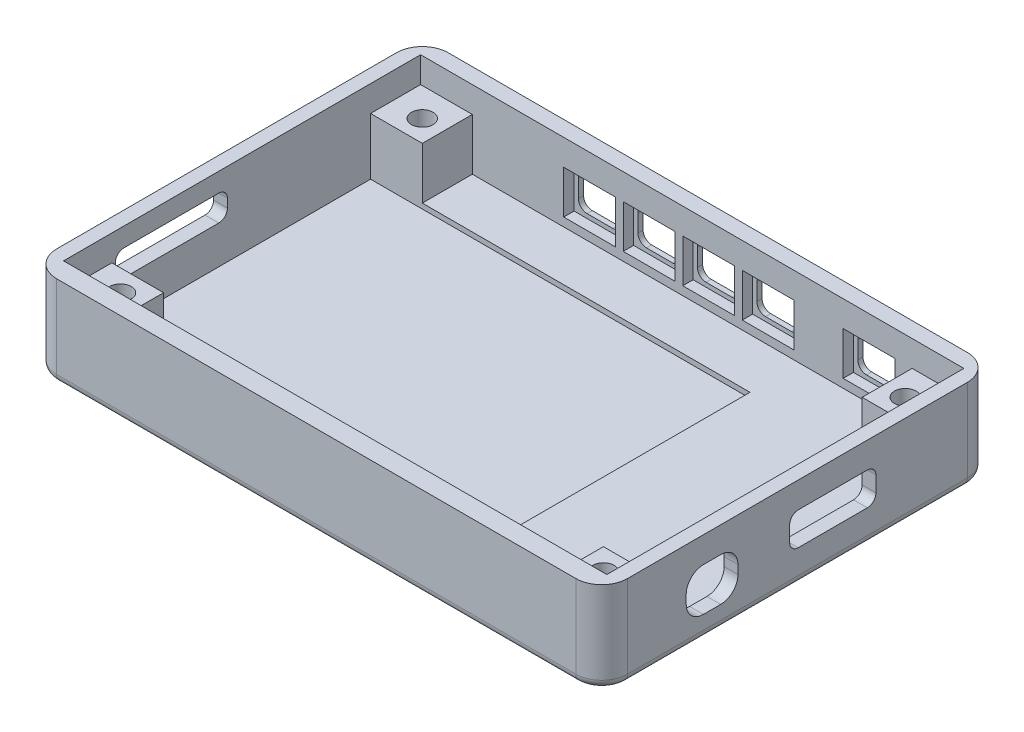
SolidWorks part; units mm, degrees
ref_plane "前视基准面" through (0, 0, 0) normal (0, 0, 1) x (1, 0, 0)
ref_plane "上视基准面" through (0, 0, 0) normal (0, 1, 0) x (1, 0, 0)
ref_plane "右视基准面" through (0, 0, 0) normal (1, 0, 0) x (0, 0, -1)
sketch "草图1" plane through (0, 0, 0) normal (0, 1, 0) x (1, 0, 0)
  line L1 (-31.5, -21) -> (31.5, -21)
  line L2 (-31.5, -21) -> (-31.5, 21)
  line L3 (-31.5, 21) -> (31.5, 21)
  line L4 (31.5, -21) -> (31.5, 21)
  line L5 (-31.5, -21) -> (31.5, 21) construction
  line L6 (-31.5, 21) -> (31.5, -21) construction
  point P0 (0, 0)
  dimension "D1" = 63
  dimension "D2" = 42
extrude "底" add sketch "草图1" against normal blind 1.6
sketch "草图2" plane through (0, 0, 0) normal (0, 1, 0) x (1, 0, 0)
  line L0 (-31.5, 21) -> (-31.5, -21) construction
  line L1 (-31.5, -15) -> (12.5, -15)
  line L2 (-31.5, -15) -> (-31.5, 15)
  line L3 (-31.5, 15) -> (12.5, 15)
  line L4 (12.5, -15) -> (12.5, 15)
  line L5 (-31.5, -15) -> (12.5, 15) construction
  line L6 (-31.5, 15) -> (12.5, -15) construction
  line L7 (31.5, 21) -> (-31.5, 21) construction
  line L8 (-31.5, -21) -> (31.5, -21) construction
  point P0 (-19.9597, 0.5003)
  dimension "D1" = 44
  dimension "D2" = 6
  dimension "D3" = 0
  dimension "D4" = 6
extrude "电池槽" cut sketch "草图2" against normal blind 0.6
sketch "草图4" plane through (0, -1.6, 0) normal (0, -1, 0) x (-1, 0, 0)
  line L0 (-31.5, 21) -> (-31.5, -21)
  line L1 (-31.5, 21) -> (-33.1, 21)
  line L2 (-31.5, -21) -> (-33.1, -21)
  line L3 (-33.1, 21) -> (-33.1, -21)
  line L4 (31.5, 21) -> (31.5, -21)
  line L5 (31.5, 21) -> (33.1, 21)
  line L6 (31.5, -21) -> (33.1, -21)
  line L7 (33.1, 21) -> (33.1, -21)
  dimension "D1" = 1.6
  dimension "D2" = 1.6
extrude "侧边" add sketch "草图4" against normal blind 10.6
sketch "草图5" plane through (0, 0, 0) normal (0, 1, 0) x (1, 0, 0)
  line L0 (-31.5, 21) -> (-31.5, 15)
  line L1 (-31.5, 21) -> (-25.5, 21)
  line L2 (-31.5, 15) -> (-25.5, 15)
  line L3 (-25.5, 21) -> (-25.5, 15)
  line L4 (-31.5, 21) -> (-31.5, 15) construction
  line L5 (25.5, 21) -> (25.5, 15)
  line L6 (25.5, 21) -> (31.5, 21)
  line L7 (25.5, 15) -> (31.5, 15)
  line L8 (31.5, 21) -> (31.5, 15)
  line L9 (-31.5, -15) -> (-31.5, -21)
  line L10 (-31.5, -15) -> (-25.5, -15)
  line L11 (-31.5, -21) -> (-25.5, -21)
  line L12 (-25.5, -15) -> (-25.5, -21)
  line L13 (25.5, -15) -> (25.5, -21)
  line L14 (25.5, -15) -> (31.5, -15)
  line L15 (25.5, -21) -> (31.5, -21)
  line L16 (31.5, -15) -> (31.5, -21)
  dimension "D1" = 6
  dimension "D2" = 6
  dimension "D3" = 6
  dimension "D4" = 6
extrude "螺丝固定" add sketch "草图5" along normal offset from surface (6 mm away) 3 up to face at (-32.3, 9, 0)
sketch "草图6" plane through (0, 9, 0) normal (0, 1, 0) x (1, 0, 0)
  line L0 (-25.5, 15) -> (-25.5, 21) construction
  line L1 (-31.5, 15) -> (-25.5, 15) construction
  circle A0 centre (-28, 17.5) radius 1.25
  circle A1 centre (28, 17.5) radius 1.25
  circle A2 centre (28, -17.5) radius 1.25
  circle A3 centre (-28, -17.5) radius 1.25
  dimension "D1" = 2.5
  dimension "D2" = 2.5
  dimension "D3" = 2.5
  dimension "D4" = 2
  dimension "D5" = 2
extrude "螺丝孔" cut sketch "草图6" against normal up to surface (9 mm away) up to face at (7.3333, 0, 0)
sketch "草图8" plane through (0, 0, 0) normal (0, 1, 0) x (1, 0, 0)
  line L0 (25.5, 21) -> (25.5, 15) construction
  line L1 (-30.5, 20) -> (-25.5, 20)
  line L2 (-30.5, 20) -> (-30.5, 15)
  line L3 (-30.5, 15) -> (-25.5, 15)
  line L4 (-25.5, 20) -> (-25.5, 15)
  line L5 (-30.5, 20) -> (-25.5, 15) construction
  line L6 (-30.5, 15) -> (-25.5, 20) construction
  line L7 (30.5, 20) -> (25.5, 20)
  line L8 (30.5, 20) -> (30.5, 15)
  line L9 (30.5, 15) -> (25.5, 15)
  line L10 (25.5, 20) -> (25.5, 15)
  line L11 (30.5, 20) -> (25.5, 15) construction
  line L12 (30.5, 15) -> (25.5, 20) construction
  line L14 (-30.5, -20) -> (-25.5, -20)
  line L15 (-30.5, -20) -> (-30.5, -15)
  line L16 (-30.5, -15) -> (-25.5, -15)
  line L17 (-25.5, -20) -> (-25.5, -15)
  line L18 (-30.5, -20) -> (-25.5, -15) construction
  line L19 (-30.5, -15) -> (-25.5, -20) construction
  line L20 (30.5, -20) -> (25.5, -20)
  line L21 (30.5, -20) -> (30.5, -15)
  line L22 (30.5, -15) -> (25.5, -15)
  line L23 (25.5, -20) -> (25.5, -15)
  line L24 (30.5, -20) -> (25.5, -15) construction
  line L25 (30.5, -15) -> (25.5, -20) construction
  circle A0 centre (28, 17.5) radius 1.25 construction
  circle A1 centre (28, -17.5) radius 1.25 construction
  circle A2 centre (-28, -17.5) radius 1.25 construction
  circle A3 centre (-28, 17.5) radius 1.25 construction
  circle A4 centre (28, 17.5) radius 1.25 construction
  circle A5 centre (28, -17.5) radius 1.25 construction
  circle A6 centre (-28, -17.5) radius 1.25 construction
  circle A7 centre (-28, 17.5) radius 1.25 construction
sketch "草图9" plane through (0, 0, -21) normal (0, 0, -1) x (-1, 0, 0)
  line L0 (-33.1, 9) -> (-33.1, -1.6)
  line L1 (-33.1, 9) -> (33.1, 9)
  line L2 (-33.1, -1.6) -> (33.1, -1.6)
  line L3 (33.1, 9) -> (33.1, -1.6)
extrude "凸台-拉伸4" add sketch "草图9" along normal blind 1.6
sketch "草图10" plane through (0, 0, -21) normal (0, 0, 1) x (1, 0, 0)
  line L1 (17.5, 1) -> (23.5, 1)
  line L2 (17.5, 1) -> (17.5, 6)
  line L3 (17.5, 6) -> (23.5, 6)
  line L4 (23.5, 1) -> (23.5, 6)
  line L5 (17.5, 1) -> (23.5, 6) construction
  line L6 (17.5, 6) -> (23.5, 1) construction
  line L7 (25.5, 0) -> (-25.5, 0) construction
  line L8 (25.5, 6) -> (25.5, 0) construction
  line L9 (5.8, 1) -> (11.8, 1)
  line L10 (5.8, 1) -> (5.8, 6)
  line L11 (5.8, 6) -> (11.8, 6)
  line L12 (11.8, 1) -> (11.8, 6)
  line L13 (5.8, 1) -> (11.8, 6) construction
  line L14 (5.8, 6) -> (11.8, 1) construction
  line L15 (-1.1, 1) -> (4.9, 1)
  line L16 (-1.1, 1) -> (-1.1, 6)
  line L17 (-1.1, 6) -> (4.9, 6)
  line L18 (4.9, 1) -> (4.9, 6)
  line L19 (-1.1, 1) -> (4.9, 6) construction
  line L20 (-1.1, 6) -> (4.9, 1) construction
  line L21 (-8, 1) -> (-2, 1)
  line L22 (-8, 1) -> (-8, 6)
  line L23 (-8, 6) -> (-2, 6)
  line L24 (-2, 1) -> (-2, 6)
  line L25 (-8, 1) -> (-2, 6) construction
  line L26 (-8, 6) -> (-2, 1) construction
  line L27 (-14.9, 1) -> (-8.9, 1)
  line L28 (-14.9, 1) -> (-14.9, 6)
  line L29 (-14.9, 6) -> (-8.9, 6)
  line L30 (-8.9, 1) -> (-8.9, 6)
  line L31 (-14.9, 1) -> (-8.9, 6) construction
  line L32 (-14.9, 6) -> (-8.9, 1) construction
  point P0 (20.5, 3.5)
  point P11 (8.8, 3.5)
  point P16 (1.9, 3.5)
  point P21 (-5, 3.5)
  point P26 (-11.9, 3.5)
  dimension "D1" = 6
  dimension "D2" = 5
  dimension "D3" = 5
  dimension "D4" = 3.5
  dimension "D5" = 2
  dimension "D6" = 4
extrude "按键底" cut sketch "草图10" against normal blind 1
sketch "草图12" plane through (0, 0, -22) normal (0, 0, 1) x (1, 0, 0)
  line L0 (17.5, 6) -> (23.5, 1) construction
  line L1 (6.3, 2.5) -> (6.3, 4.5)
  line L2 (19, 1.5) -> (22, 1.5)
  line L3 (18, 2.5) -> (18, 4.5)
  line L4 (23.5, 1) -> (23.5, 6)
  line L5 (23.5, 6) -> (17.5, 6)
  line L6 (17.5, 6) -> (17.5, 1)
  line L7 (17.5, 1) -> (23.5, 1)
  line L8 (23.5, 1) -> (23.5, 6) construction
  line L9 (23.5, 6) -> (17.5, 6) construction
  line L10 (17.5, 6) -> (17.5, 1) construction
  line L11 (17.5, 1) -> (23.5, 1) construction
  line L12 (19, 5.5) -> (22, 5.5)
  line L13 (23, 2.5) -> (23, 4.5)
  line L14 (18, 1.5) -> (23, 5.5) construction
  line L15 (18, 5.5) -> (23, 1.5) construction
  line L16 (7.3, 1.5) -> (10.3, 1.5)
  line L17 (7.3, 5.5) -> (10.3, 5.5)
  line L18 (11.3, 2.5) -> (11.3, 4.5)
  line L19 (-0.6, 2.5) -> (-0.6, 4.5)
  line L20 (0.4, 1.5) -> (3.4, 1.5)
  line L21 (0.4, 5.5) -> (3.4, 5.5)
  line L22 (4.4, 2.5) -> (4.4, 4.5)
  line L23 (-7.5, 2.5) -> (-7.5, 4.5)
  line L24 (-6.5, 1.5) -> (-3.5, 1.5)
  line L25 (-6.5, 5.5) -> (-3.5, 5.5)
  line L26 (-2.5, 2.5) -> (-2.5, 4.5)
  line L27 (-14.4, 2.5) -> (-14.4, 4.5)
  line L28 (-13.4, 1.5) -> (-10.4, 1.5)
  line L29 (-13.4, 5.5) -> (-10.4, 5.5)
  line L30 (-9.4, 2.5) -> (-9.4, 4.5)
  arc A0 (22, 5.5) -> (23, 4.5) centre (22, 4.5) cw
  arc A1 (22, 1.5) -> (23, 2.5) centre (22, 2.5) ccw
  arc A2 (19, 1.5) -> (18, 2.5) centre (19, 2.5) cw
  arc A3 (18, 4.5) -> (19, 5.5) centre (19, 4.5) cw
  arc A4 (6.3, 4.5) -> (7.3, 5.5) centre (7.3, 4.5) cw
  arc A5 (7.3, 1.5) -> (6.3, 2.5) centre (7.3, 2.5) cw
  arc A6 (10.3, 5.5) -> (11.3, 4.5) centre (10.3, 4.5) cw
  arc A7 (10.3, 1.5) -> (11.3, 2.5) centre (10.3, 2.5) ccw
  arc A8 (-0.6, 4.5) -> (0.4, 5.5) centre (0.4, 4.5) cw
  arc A9 (0.4, 1.5) -> (-0.6, 2.5) centre (0.4, 2.5) cw
  arc A10 (3.4, 5.5) -> (4.4, 4.5) centre (3.4, 4.5) cw
  arc A11 (3.4, 1.5) -> (4.4, 2.5) centre (3.4, 2.5) ccw
  arc A12 (-7.5, 4.5) -> (-6.5, 5.5) centre (-6.5, 4.5) cw
  arc A13 (-6.5, 1.5) -> (-7.5, 2.5) centre (-6.5, 2.5) cw
  arc A14 (-3.5, 5.5) -> (-2.5, 4.5) centre (-3.5, 4.5) cw
  arc A15 (-3.5, 1.5) -> (-2.5, 2.5) centre (-3.5, 2.5) ccw
  arc A16 (-14.4, 4.5) -> (-13.4, 5.5) centre (-13.4, 4.5) cw
  arc A17 (-13.4, 1.5) -> (-14.4, 2.5) centre (-13.4, 2.5) cw
  arc A18 (-10.4, 5.5) -> (-9.4, 4.5) centre (-10.4, 4.5) cw
  arc A19 (-10.4, 1.5) -> (-9.4, 2.5) centre (-10.4, 2.5) ccw
  point P2 (20.5, 3.5)
  dimension "D4" = 1
  dimension "D2" = 5
  dimension "D3" = 4
  dimension "D1" = 0
  dimension "D5" = 2
  dimension "D6" = 4
extrude "按键头" cut sketch "草图12" against normal up to next
fillet "圆角4" radius 1 3 edges at (-33.1, -1.6, -0.8) (33.1, -1.6, -0.8) (0, -1.6, -22.6)
fillet "圆角5" radius 3 4 edges at (-32.8071, -1.3071, -22.3071) (32.8071, -1.3071, -22.3071) (33.1, 4.2, -22.6) (-33.1, 4.2, -22.6)
sketch "草图15" plane through (0, 9, 0) normal (0, 1, 0) x (1, 0, 0)
  line L8 (-31.5, 21) -> (31.5, 21)
  line L10 (-31.5, 21) -> (31.5, 21)
  line L16 (33.1, -21) -> (33.1, 19.6)
  line L17 (30.1, 22.6) -> (-30.1, 22.6)
  line L18 (-33.1, 19.6) -> (-33.1, -21)
  line L19 (-33.1, -21) -> (-31.5, -21)
  line L22 (-31.5, -21) -> (-31.5, 21)
  line L28 (31.5, 21) -> (31.5, -21)
  line L31 (31.5, -21) -> (33.1, -21)
  line L32 (33.1, -21) -> (33.1, 19.6)
  line L33 (30.1, 22.6) -> (-30.1, 22.6)
  line L34 (-33.1, 19.6) -> (-33.1, -21)
  line L35 (-33.1, -21) -> (-31.5, -21)
  line L38 (-31.5, -21) -> (-31.5, 21)
  line L44 (31.5, 21) -> (31.5, -21)
  line L47 (31.5, -21) -> (33.1, -21)
  arc A2 (33.1, 19.6) -> (30.1, 22.6) centre (30.1, 19.6) ccw
  arc A3 (-30.1, 22.6) -> (-33.1, 19.6) centre (-30.1, 19.6) ccw
  arc A4 (33.1, 19.6) -> (30.1, 22.6) centre (30.1, 19.6) ccw
  arc A5 (-30.1, 22.6) -> (-33.1, 19.6) centre (-30.1, 19.6) ccw
  dimension "D1" = 0
sketch "草图16" plane through (-31.5, 0, 0) normal (1, 0, 0) x (0, 0, -1)
  line L1 (-14.6, 5.8) -> (-14.6, 4.8)
  line L2 (-1.6, 5.8) -> (-1.6, 4.8)
  line L3 (-13.6, 3.8) -> (-2.6, 3.8)
  line L4 (-21, 9) -> (21, 9) construction
  line L5 (-15, 6) -> (-15, -0.6) construction
  line L6 (-13.6, 6.8) -> (-2.6, 6.8)
  arc A0 (-14.6, 4.8) -> (-13.6, 3.8) centre (-13.6, 4.8) ccw
  arc A1 (-1.6, 4.8) -> (-2.6, 3.8) centre (-2.6, 4.8) cw
  arc A2 (-13.6, 6.8) -> (-14.6, 5.8) centre (-13.6, 5.8) ccw
  arc A3 (-2.6, 6.8) -> (-1.6, 5.8) centre (-2.6, 5.8) cw
  point P10 (-14.6, 3.8)
  point P13 (-1.6, 3.8)
  dimension "D4" = 1
  dimension "D2" = 1
  dimension "D1" = 13
  dimension "D3" = 0.4
  dimension "D5" = 2.2
extrude "tf口" cut sketch "草图16" against normal up to next
sketch "草图17" plane through (31.5, 0, 0) normal (-1, 0, 0) x (0, 0, 1)
  line L1 (7, 4) -> (7, 3)
  line L2 (13, 4) -> (13, 3)
  line L3 (9, 1) -> (11, 1)
  line L4 (-21, 9) -> (21, 9) construction
  line L5 (15, -0.6) -> (15, 6) construction
  line L7 (1, 5) -> (1, 3.2)
  line L8 (-9, 5) -> (-9, 3.2)
  line L9 (0, 2.2) -> (-8, 2.2)
  line L10 (-8, 6) -> (0, 6)
  line L12 (9, 6) -> (11, 6)
  arc A0 (13, 3) -> (11, 1) centre (11, 3) cw
  arc A1 (7, 3) -> (9, 1) centre (9, 3) ccw
  arc A2 (1, 3.2) -> (0, 2.2) centre (0, 3.2) cw
  arc A3 (-9, 3.2) -> (-8, 2.2) centre (-8, 3.2) ccw
  arc A4 (0, 6) -> (1, 5) centre (0, 5) cw
  arc A5 (-8, 6) -> (-9, 5) centre (-8, 5) ccw
  arc A6 (11, 6) -> (13, 4) centre (11, 4) cw
  arc A7 (9, 6) -> (7, 4) centre (9, 4) ccw
  point P10 (13, 1)
  point P13 (7, 1)
  point P14 (1, 6)
  point P22 (1, 2.2)
  point P25 (-9, 2.2)
  dimension "D4" = 2
  dimension "D8" = 1
  dimension "D2" = 1
  dimension "D7" = 2
  dimension "D1" = 6
  dimension "D3" = 2
  dimension "D5" = 10
  dimension "D6" = 14
  dimension "D9" = 3
  dimension "D10" = 1.8
  dimension "D11" = 1
extrude "耳机和usb口" cut sketch "草图17" against normal up to next
sketch "草图18" plane through (0, 0, 21) normal (0, 0, 1) x (1, 0, 0)
  line L0 (33.1, 9) -> (33.1, -0.6) construction
  line L1 (-32.1, -1.6) -> (32.1, -1.6) construction
  line L2 (-33.1, 9) -> (-33.1, -0.6) construction
  line L3 (33.1, 9) -> (33.1, -0.6)
  line L4 (-32.1, -1.6) -> (32.1, -1.6)
  line L5 (-33.1, 9) -> (-33.1, -0.6)
  line L6 (-33.1, 9) -> (33.1, 9)
  arc A0 (32.1, -1.6) -> (33.1, -0.6) centre (32.1, -0.6) ccw construction
  arc A1 (-33.1, -0.6) -> (-32.1, -1.6) centre (-32.1, -0.6) ccw construction
  arc A2 (32.1, -1.6) -> (33.1, -0.6) centre (32.1, -0.6) ccw
  arc A3 (-33.1, -0.6) -> (-32.1, -1.6) centre (-32.1, -0.6) ccw
extrude "封底" add sketch "草图18" along normal blind 1.8
fillet "圆角7" radius 3 2 edges at (33.1, 4.2, 22.8) (-33.1, 4.2, 22.8) tangent propagation no
fillet "圆角8" radius 1 3 edges at (-31.1705, -1.6, 22.6025) (31.1705, -1.6, 22.6025) (0, -1.6, 22.8)
sketch "草图19" plane through (0, 0, 21) normal (0, 0, -1) x (-1, 0, 0)
  line L8 (31.5, 9) -> (-31.5, 9)
  line L9 (-31.5, 9) -> (-31.5, 6)
  line L10 (-31.5, 6) -> (-25.5, 6)
  line L11 (-25.5, 6) -> (-25.5, 0)
  line L12 (-25.5, 0) -> (25.5, 0)
  line L13 (25.5, 0) -> (25.5, 6)
  line L14 (25.5, 6) -> (31.5, 6)
  line L15 (31.5, 6) -> (31.5, 9)
  line L16 (31.5, 9) -> (-31.5, 9)
  line L17 (-31.5, 9) -> (-31.5, 6)
  line L18 (-31.5, 6) -> (-25.5, 6)
  line L19 (-25.5, 6) -> (-25.5, 0)
  line L20 (-25.5, 0) -> (25.5, 0)
  line L21 (25.5, 0) -> (25.5, 6)
  line L22 (25.5, 6) -> (31.5, 6)
  line L23 (31.5, 6) -> (31.5, 9)
  dimension "D1" = 0
extrude "凸台-拉伸5" add sketch "草图19" along normal blind 0.4
sketch "草图24" plane through (0, 0, 0) normal (0, 1, 0) x (1, 0, 0)
  line L12 (-25.5, -15) -> (-25.5, -20.6)
  line L13 (-25.5, -20.6) -> (25.5, -20.6)
  line L14 (25.5, -20.6) -> (25.5, -15)
  line L15 (25.5, -15) -> (31.5, -15)
  line L16 (31.5, -15) -> (31.5, 15)
  line L17 (31.5, 15) -> (25.5, 15)
  line L18 (25.5, 15) -> (25.5, 21)
  line L19 (25.5, 21) -> (-25.5, 21)
  line L20 (-25.5, 21) -> (-25.5, 15)
  line L21 (-25.5, 15) -> (12.5, 15)
  line L22 (12.5, 15) -> (12.5, -15)
  line L23 (12.5, -15) -> (-25.5, -15)
  line L24 (-25.5, -15) -> (-25.5, -20.6)
  line L25 (-25.5, -20.6) -> (25.5, -20.6)
  line L26 (25.5, -20.6) -> (25.5, -15)
  line L27 (25.5, -15) -> (31.5, -15)
  line L28 (31.5, -15) -> (31.5, 15)
  line L29 (31.5, 15) -> (25.5, 15)
  line L30 (25.5, 15) -> (25.5, 21)
  line L32 (-25.5, 21) -> (-25.5, 15)
  line L33 (-25.5, 15) -> (12.5, 15)
  line L34 (12.5, 15) -> (12.5, -15)
  line L35 (12.5, -15) -> (-25.5, -15)
  line L37 (25.5, 21) -> (-25.5, 21)
  dimension "D1" = 0
sketch "草图25" plane through (0, 0, 0) normal (0, 1, 0) x (1, 0, 0)
  circle A0 centre (25.5, 12) radius 1
  point P0 (28, 17.5)
  dimension "D1" = 2
  dimension "D2" = 2.5
  dimension "D3" = 5.5
extrude "BOOT孔" cut sketch "草图25" against normal up to next
sketch "草图27" plane through (0, 0, -21) normal (0, 0, 1) x (1, 0, 0)
  line L4 (5.8, 1) -> (11.8, 1)
  line L5 (11.8, 1) -> (11.8, 6)
  line L6 (11.8, 6) -> (5.8, 6)
  line L7 (5.8, 6) -> (5.8, 1)
  line L8 (31.5, 6) -> (31.5, 9)
  line L9 (31.5, 9) -> (-31.5, 9)
  line L10 (-31.5, 9) -> (-31.5, 6)
  line L11 (-31.5, 6) -> (-25.5, 6)
  line L12 (-25.5, 6) -> (-25.5, 0)
  line L13 (-25.5, 0) -> (25.5, 0)
  line L14 (25.5, 0) -> (25.5, 6)
  line L15 (25.5, 6) -> (31.5, 6)
  line L16 (31.5, 6) -> (31.5, 9)
  line L17 (31.5, 9) -> (-31.5, 9)
  line L18 (-31.5, 9) -> (-31.5, 6)
  line L19 (-31.5, 6) -> (-25.5, 6)
  line L20 (-25.5, 6) -> (-25.5, 0)
  line L21 (-25.5, 0) -> (25.5, 0)
  line L22 (25.5, 0) -> (25.5, 6)
  line L23 (25.5, 6) -> (31.5, 6)
  line L24 (5.8, 1) -> (11.8, 1)
  line L25 (11.8, 1) -> (11.8, 6)
  line L26 (11.8, 6) -> (5.8, 6)
  line L27 (5.8, 6) -> (5.8, 1)
  line L28 (17.5, 1) -> (23.5, 1)
  line L29 (23.5, 1) -> (23.5, 6)
  line L30 (23.5, 6) -> (17.5, 6)
  line L31 (17.5, 6) -> (17.5, 1)
  line L32 (17.5, 1) -> (23.5, 1)
  line L33 (23.5, 1) -> (23.5, 6)
  line L34 (23.5, 6) -> (17.5, 6)
  line L35 (17.5, 6) -> (17.5, 1)
  line L36 (-14.9, 1) -> (-8.9, 1)
  line L37 (-8.9, 1) -> (-8.9, 6)
  line L38 (-8.9, 6) -> (-14.9, 6)
  line L39 (-14.9, 6) -> (-14.9, 1)
  line L40 (-14.9, 1) -> (-8.9, 1)
  line L41 (-8.9, 1) -> (-8.9, 6)
  line L42 (-8.9, 6) -> (-14.9, 6)
  line L43 (-14.9, 6) -> (-14.9, 1)
  line L44 (-8, 1) -> (-2, 1)
  line L45 (-2, 1) -> (-2, 6)
  line L46 (-2, 6) -> (-8, 6)
  line L47 (-8, 6) -> (-8, 1)
  line L48 (-8, 1) -> (-2, 1)
  line L49 (-2, 1) -> (-2, 6)
  line L50 (-2, 6) -> (-8, 6)
  line L51 (-8, 6) -> (-8, 1)
  line L52 (-1.1, 1) -> (4.9, 1)
  line L53 (4.9, 1) -> (4.9, 6)
  line L54 (4.9, 6) -> (-1.1, 6)
  line L55 (-1.1, 6) -> (-1.1, 1)
  line L56 (-1.1, 1) -> (4.9, 1)
  line L57 (4.9, 1) -> (4.9, 6)
  line L58 (4.9, 6) -> (-1.1, 6)
  line L59 (-1.1, 6) -> (-1.1, 1)
  dimension "D1" = 0
  dimension "D2" = 0
  dimension "D3" = 0
  dimension "D4" = 0
  dimension "D5" = 0
  dimension "D6" = 0
extrude "凸台-拉伸8" add sketch "草图27" along normal blind 0.2
